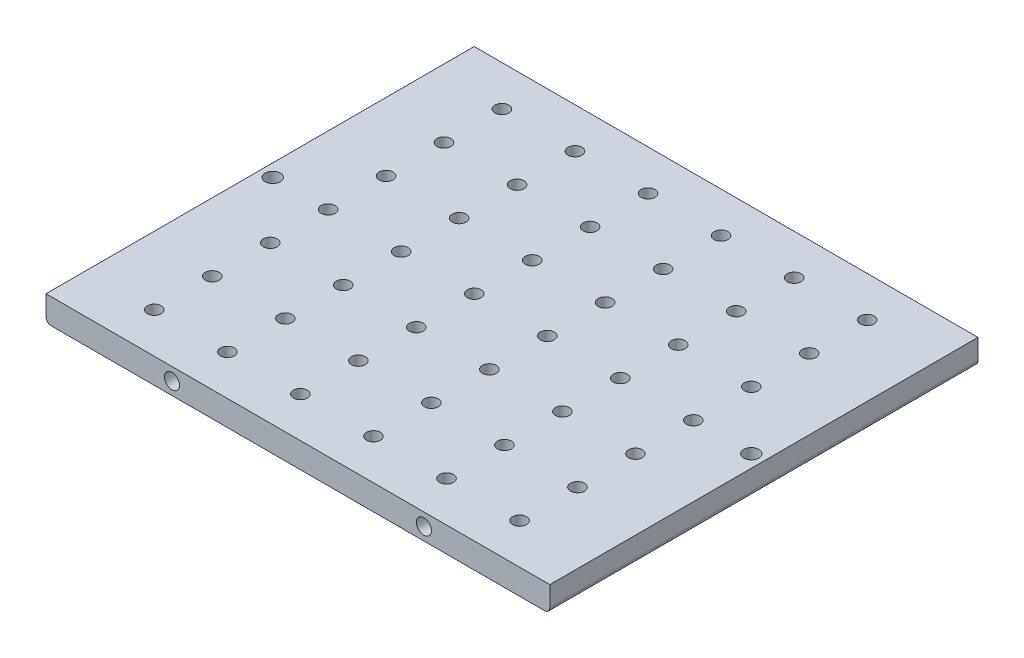
SolidWorks part; units mm, degrees
ref_plane "Plan de face" through (0, 0, 0) normal (0, 0, 1) x (1, 0, 0)
ref_plane "Plan de dessus" through (0, 0, 0) normal (0, 1, 0) x (1, 0, 0)
ref_plane "Plan de droite" through (0, 0, 0) normal (1, 0, 0) x (0, 0, -1)
sketch "Esquisse1" plane through (0, 0, 0) normal (0, 1, 0) x (1, 0, 0)
  line L1 (-50, -42.5) -> (50, -42.5)
  line L2 (-50, -42.5) -> (-50, 42.5)
  line L3 (-50, 42.5) -> (50, 42.5)
  line L4 (50, -42.5) -> (50, 42.5)
  line L5 (-50, -42.5) -> (50, 42.5) construction
  line L6 (-50, 42.5) -> (50, -42.5) construction
  point P0 (0, 0)
  dimension "D1" = 85
  dimension "D2" = 100
extrude "Boss.-Extru.1" add sketch "Esquisse1" along normal blind 5
sketch "Esquisse2" plane through (0, 0, 42.5) normal (0, 0, 1) x (1, 0, 0)
  line L0 (-50, 2.5) -> (29.6548, 2.5) construction
  line L3 (-50, 5) -> (-50, 0) construction
  line L5 (0, 0) -> (0, 17.0048) construction
  circle A0 centre (-25, 2.5) radius 1.5
  circle A1 centre (25, 2.5) radius 1.5
  dimension "D2" = 25
  dimension "D3" = 3
extrude "Enlèv. mat.-Extru.1" cut sketch "Esquisse2" against normal up to surface (85 mm away) up to face at (0, 2.5, -42.5)
sketch "Esquisse3" plane through (0, 0, 0) normal (0, 1, 0) x (1, 0, 0)
  line L1 (-40, 8) -> (25, 8) construction
  line L2 (-40, 8) -> (-40, 38) construction
  line L3 (-40, 38) -> (25, 38) construction
  line L4 (25, 8) -> (25, 38) construction
  line L5 (-40, 8) -> (25, 38) construction
  line L6 (-40, 38) -> (25, 8) construction
  line L7 (50, 42.5) -> (-50, 42.5) construction
  line L8 (-50, 42.5) -> (-50, -42.5) construction
  circle A0 centre (-36.5, 34.5) radius 1.375
  point P0 (-7.5, 23)
  dimension "D3" = 2.75
  dimension "D4" = 3.5
  dimension "D1" = 65
  dimension "D2" = 30
  dimension "D5" = 3.5
  dimension "D6" = 4.5
  dimension "D7" = 10
extrude "Enlèv. mat.-Extru.2" cut sketch "Esquisse3" along normal up to surface (5 mm away) up to face at (0, 5, 0)
pattern_linear "Répétition linéaire1" count 7 spacing 11.5 along (0, 0, 1) count 6 spacing 14.5 along (1, 0, 0) of "Enlèv. mat.-Extru.2"
sketch "Esquisse4" plane through (0, 0, 0) normal (0, 1, 0) x (1, 0, 0)
  line L0 (0, 42.5) -> (0, -48.0193) construction
  line L1 (50, 42.5) -> (-50, 42.5) construction
  line L2 (-50, 0) -> (96.9461, 0) construction
  line L3 (-50, 42.5) -> (-50, -42.5) construction
  circle A0 centre (-47.5, 0) radius 1.5
  circle A1 centre (47.5, 0) radius 1.5
  dimension "D1" = 3
  dimension "D2" = 2.5
extrude "Enlèv. mat.-Extru.3" cut sketch "Esquisse4" along normal up to surface (5 mm away) up to face at (-22, 5, -24.375)
fillet "Congé1" radius 1 2 edges at (50, 0, 0) (-50, 0, 0)
sketch "Esquisse5" [suppressed] plane through (0, 0, 0) normal (0, -1, 0) x (1, 0, 0)
  line L0 (50, 42.5) -> (50, -42.5) construction
  line L1 (19.4, -42.5) -> (33, -42.5)
  line L2 (19.4, -42.5) -> (19.4, -35.9)
  line L3 (19.4, -35.9) -> (33, -35.9)
  line L4 (33, -42.5) -> (33, -35.9)
  line L5 (19.4, -42.5) -> (33, -35.9) construction
  line L6 (19.4, -35.9) -> (33, -42.5) construction
  line L7 (50, -42.5) -> (-50, -42.5) construction
  point P0 (26.2, -39.2)
  dimension "D1" = 17
  dimension "D2" = 6.6
  dimension "D3" = 13.6
extrude "Enlèv. mat.-Extru.4" [suppressed] cut sketch "Esquisse5" against normal up to surface (5 mm away)
pattern_linear "Répétition linéaire2" [suppressed] count 3 spacing 16.55 of bodies 106
sketch "Esquisse7" [suppressed] plane through (0, 0, 0) normal (0, -1, 0) x (-1, 0, 0)
  line L0 (-50, 42.5) -> (-33, 42.5) construction
  line L1 (-29, 28.83) -> (-37, 28.83)
  line L2 (-29, 28.83) -> (-29, 26.13)
  line L3 (-29, 26.13) -> (-37, 26.13)
  line L4 (-37, 28.83) -> (-37, 26.13)
  line L5 (-29, 28.83) -> (-37, 26.13) construction
  line L6 (-29, 26.13) -> (-37, 28.83) construction
  line L7 (-50, -42.5) -> (-50, 42.5) construction
  point P0 (-33, 27.48)
  dimension "D1" = 2.7
  dimension "D2" = 8
  dimension "D3" = 13.67
  dimension "D4" = 13
extrude "Enlèv. mat.-Extru.5" [suppressed] cut sketch "Esquisse7" against normal up to surface (5 mm away)
pattern_linear "Répétition linéaire3" [suppressed] count 2 spacing 12.77 of bodies 108
sketch "Esquisse8" [suppressed] plane through (0, 0, 0) normal (0, -1, 0) x (1, 0, 0)
  line L0 (-13.7, -42.5) -> (-50, -42.5) construction
  line L1 (-14.3, -25.1) -> (-3, -25.1)
  line L2 (-14.3, -25.1) -> (-14.3, -28.5)
  line L3 (-14.3, -28.5) -> (-3, -28.5)
  line L4 (-3, -25.1) -> (-3, -28.5)
  line L5 (-14.3, -25.1) -> (-3, -28.5) construction
  line L6 (-14.3, -28.5) -> (-3, -25.1) construction
  line L7 (50, 42.5) -> (50, -42.5) construction
  point P0 (-8.65, -26.8)
  dimension "D1" = 11.3
  dimension "D2" = 3.4
  dimension "D3" = 14
  dimension "D4" = 53
extrude "Enlèv. mat.-Extru.6" [suppressed] cut sketch "Esquisse8" against normal up to surface (5 mm away)
